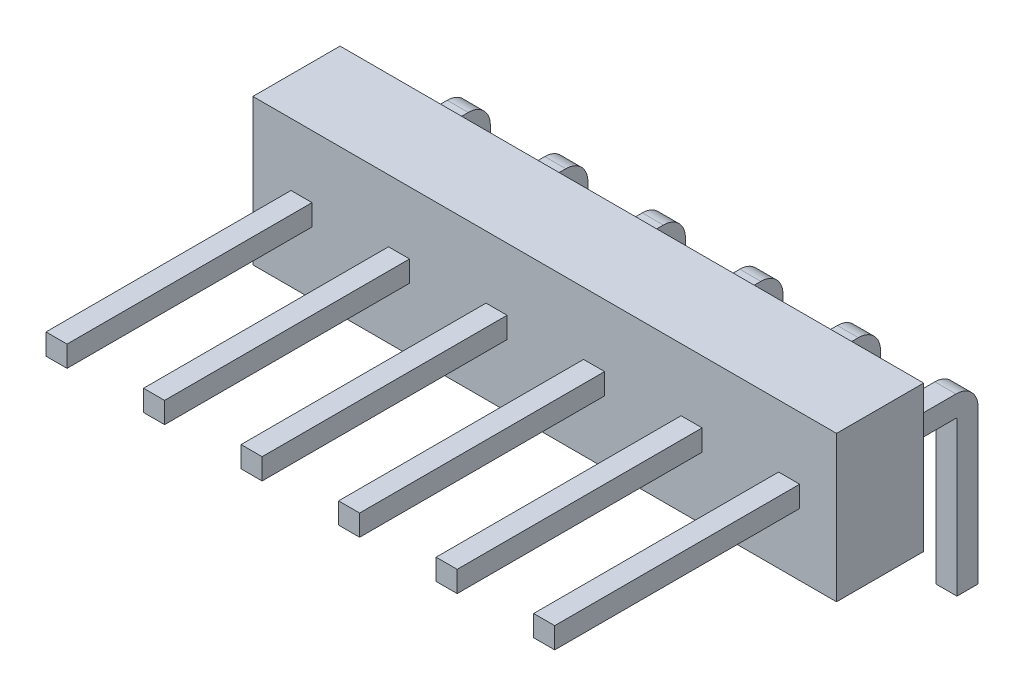
SolidWorks part; units mm, degrees
ref_plane "Front Plane" through (0, 0, 0) normal (0, 0, 1) x (1, 0, 0)
ref_plane "Top Plane" through (0, 0, 0) normal (0, 1, 0) x (1, 0, 0)
ref_plane "Right Plane" through (0, 0, 0) normal (1, 0, 0) x (0, 0, -1)
sketch "Sketch1" plane through (0, 0, 0) normal (0, 1, 0) x (1, 0, 0)
  line L1 (0, 0) -> (15.2, 0)
  line L2 (0, 0) -> (0, 2.27)
  line L3 (0, 2.27) -> (15.2, 2.27)
  line L4 (15.2, 0) -> (15.2, 2.27)
extrude "Boss-Extrude1" add sketch "Sketch1" along normal blind 3.8
sketch "Sketch2" plane through (0, 0, -2.27) normal (0, 0, -1) x (-1, 0, 0)
  line L0 (0, 1.6259) -> (-15.2, 1.6259) construction
  line L1 (0, 3.8) -> (0, 0) construction
  line L2 (-15.2, 3.8) -> (-15.2, 0) construction
  line L3 (-0.9923, 0) -> (-0.9923, 3.8) construction
  line L4 (0, 2.1741) -> (-15.2, 2.1741) construction
  line L5 (-15.2, 0) -> (0, 0) construction
  line L6 (-15.2, 3.8) -> (0, 3.8) construction
  line L7 (-0.9923, 1.9) -> (0, 1.9) construction
  line L8 (-0.9923, 1.6259) -> (-1.5405, 1.6259)
  line L9 (-0.9923, 1.6259) -> (-0.9923, 2.1741)
  line L10 (-0.9923, 2.1741) -> (-1.5405, 2.1741)
  line L11 (-1.5405, 1.6259) -> (-1.5405, 2.1741)
  line L12 (-1.2664, 1.6259) -> (-1.2664, 0) construction
  line L13 (-1.2664, 2.1741) -> (-1.2664, 3.8) construction
  line L14 (-3.5323, 1.6259) -> (-3.5323, 2.1741)
  line L15 (-3.5323, 1.6259) -> (-4.0805, 1.6259)
  line L16 (-3.5323, 2.1741) -> (-4.0805, 2.1741)
  line L17 (-4.0805, 1.6259) -> (-4.0805, 2.1741)
  line L18 (-6.0723, 1.6259) -> (-6.0723, 2.1741)
  line L19 (-6.0723, 1.6259) -> (-6.6205, 1.6259)
  line L20 (-6.0723, 2.1741) -> (-6.6205, 2.1741)
  line L21 (-6.6205, 1.6259) -> (-6.6205, 2.1741)
  line L22 (-8.6123, 1.6259) -> (-8.6123, 2.1741)
  line L23 (-8.6123, 1.6259) -> (-9.1605, 1.6259)
  line L24 (-8.6123, 2.1741) -> (-9.1605, 2.1741)
  line L25 (-9.1605, 1.6259) -> (-9.1605, 2.1741)
  line L26 (-11.1523, 1.6259) -> (-11.1523, 2.1741)
  line L27 (-11.1523, 1.6259) -> (-11.7005, 1.6259)
  line L28 (-11.1523, 2.1741) -> (-11.7005, 2.1741)
  line L29 (-11.7005, 1.6259) -> (-11.7005, 2.1741)
  line L30 (-13.6923, 1.6259) -> (-13.6923, 2.1741)
  line L31 (-13.6923, 1.6259) -> (-14.2405, 1.6259)
  line L32 (-13.6923, 2.1741) -> (-14.2405, 2.1741)
  line L33 (-14.2405, 1.6259) -> (-14.2405, 2.1741)
  dimension "D1" = 6
sketch "Sketch3" plane through (0, 0, 0) normal (1, 0, 0) x (0, 0, -1)
  line L0 (2.27, 1.9) -> (4.07, 1.9)
  line L1 (2.27, 1.6259) -> (2.27, 2.1741) construction
  line L2 (4.37, 1.6) -> (4.37, -2.4)
  line L3 (4.37, 1.6) -> (4.07, 1.6) construction
  arc A0 (4.07, 1.9) -> (4.37, 1.6) centre (4.07, 1.6) cw
sweep "Sweep1" add profiles "Sketch2" path "Sketch3"
extrude "Boss-Extrude2" add sketch "Sketch2<2>" against normal blind 8.65
sketch "Sketch2<2>" plane through (0, 0, -2.27) normal (0, 0, -1) x (-1, 0, 0) same geometry as "Sketch2"
ref_plane "Plane1" through (2.8182, 0, -2.8182) normal (-0.7071, 0, 0.7071) x (0.7071, 0, 0.7071)
ref_plane "Plane2" through (-1.5518, 0, -1.5518) normal (-0.7071, 0, -0.7071) x (-0.7071, 0, 0.7071)
ref_axis "pin1" through (1.2664, 4.7708, -4.37) along (0, -1, 0)
